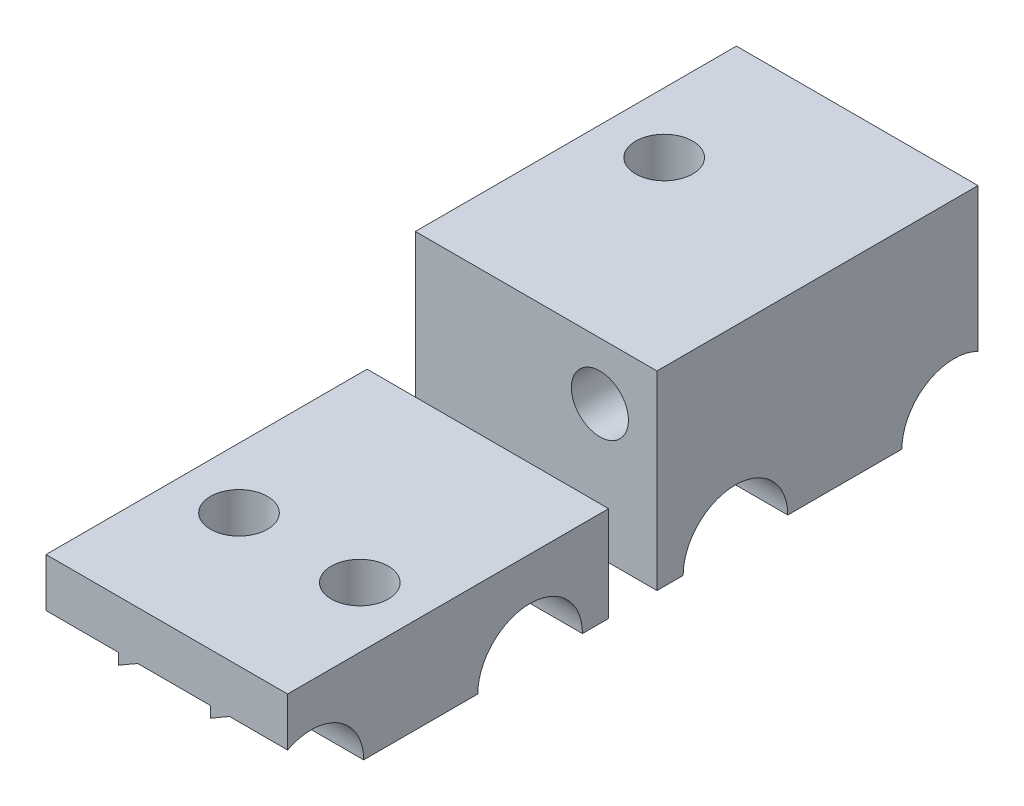
SolidWorks part; units mm, degrees
ref_plane "Front Plane" through (0, 0, 0) normal (0, 0, 1) x (1, 0, 0)
ref_plane "Top Plane" through (0, 0, 0) normal (0, 1, 0) x (1, 0, 0)
ref_plane "Right Plane" through (0, 0, 0) normal (1, 0, 0) x (0, 0, -1)
sketch "Sketch6" plane through (0, 0, 0) normal (0, 1, 0) x (1, 0, 0)
  line L0 (0, 0) -> (0, 5)
  line L1 (0, 5) -> (12.7, 5)
  line L2 (12.7, 5) -> (12.7, 2.75)
  line L6 (12.7, 2.75) -> (9.652, 2.75)
  line L7 (9.652, 2.75) -> (8.636, 2.242)
  line L8 (8.636, 2.242) -> (8.636, 2.75)
  line L9 (8.636, 2.75) -> (4.826, 2.75)
  line L10 (4.826, 2.75) -> (3.81, 2.242)
  line L11 (3.81, 2.242) -> (3.81, 2.75)
  line L12 (3.81, 2.75) -> (0, 2.75)
  line L18 (0, 0) -> (15, 0)
  dimension "D1" = 0.508
  dimension "D2" = 12.7
  dimension "D3" = 3.048
  dimension "D4" = 5
  dimension "D5" = 2.25
  dimension "D6" = 2.25
  dimension "D7" = 2.25
  dimension "D10" = 1.016
  dimension "D11" = 1.016
  dimension "D12" = 3.81
  dimension "D13" = 3.81
  dimension "D20" = 15
revolve "Revolve1" add sketch "Sketch6" angle 180 about L18 region at (6.3538, 0, -3.852)
sketch "Sketch9" plane through (0, 0, 0) normal (0, 0, 1) x (1, 0, 0)
  line L0 (0, 0) -> (0, 3.25)
  line L1 (0, 3.25) -> (0, 5)
  line L2 (0, 5) -> (12.7, 5)
  line L3 (12.7, 5) -> (12.7, 2.75)
  line L4 (12.7, 2.75) -> (12.7, 0)
  line L5 (12.7, 0) -> (0, 0)
  line L6 (0, 3.25) -> (12.7, 2.75)
  dimension "D1" = 3.25
extrude "Boss-Extrude1" add sketch "Sketch9" along normal blind 9.25 and the other way blind 9.25 contours L1 L6 L3 L2 region at (6.6146, 3.9948, 0)
extrude "Boss-Extrude2" add sketch "Sketch9<3>" along normal blind 5.75 from offset 3.5 contours L6 L0 L5 L4 region at (6.1736, 1.5035, 0)
sketch "Sketch9<3>" plane through (0, 0, 0) normal (0, 0, 1) x (1, 0, 0) same geometry as "Sketch9"
extrude "Boss-Extrude3" add sketch "Sketch9<4>" against normal blind 5.75 from offset 3.5 contours L6 L0 L5 L4 region at (6.1736, 1.5035, 0) offset against normal yes
sketch "Sketch9<4>" plane through (0, 0, 0) normal (0, 0, 1) x (1, 0, 0) same geometry as "Sketch9"
sketch "Sketch14" plane through (0, 0, 0) normal (-1, 0, 0) x (0, 0, 1)
  line L0 (-9.25, 5) -> (9.25, 5) construction
  line L1 (-9.25, 0) -> (-6.75, 0)
  line L2 (-9.25, 0) -> (-9.25, 5)
  line L3 (-9.25, 5) -> (-6.75, 5)
  line L4 (-6.75, 0) -> (-6.75, 5)
  dimension "D1" = 2.5
extrude "Cut-Extrude10" cut sketch "Sketch14" against normal through all
ref_plane "Plane3" through (0, 0, -5.75) normal (0, 0, 1) x (1, 0, 0)
mirror "Mirror4" about plane through (0, 0, -5.75) normal (0, 0, 1) of bodies 150 146
sketch "Sketch13" plane through (0, 0, 0) normal (-1, 0, 0) x (0, 0, 1)
  line L0 (-2.75, 0) -> (-8.75, 0) construction
  line L1 (-2.75, 0) -> (2.75, 0)
  line L2 (-2.75, 0) -> (-2.75, 2.75)
  line L3 (-2.75, 2.75) -> (2.75, 2.75)
  line L4 (2.75, 0) -> (2.75, 2.75)
  point P6 (0, 0)
  dimension "D1" = 5.5
  dimension "D2" = 2.75
extrude "Cut-Extrude9" cut sketch "Sketch13" against normal blind 1.75
sketch "Sketch15" plane through (0, 5, 0) normal (0, 1, 0) x (1, 0, 0)
  line L0 (0, 20.75) -> (0, -9.25) construction
  line L1 (12.7, 20.75) -> (0, 20.75)
  line L2 (12.7, 20.75) -> (12.7, 12.75)
  line L3 (12.7, 12.75) -> (0, 12.75)
  line L4 (0, 20.75) -> (0, 12.75)
  dimension "D1" = 8
extrude "Cut-Extrude11" cut sketch "Sketch15" against normal through all
sketch "Sketch16" plane through (0, 0, 0) normal (-1, 0, 0) x (0, 0, 1)
  line L0 (-12.75, 5) -> (9.25, 5) construction
  line L1 (9.25, 0) -> (4.1274, 0)
  line L2 (9.25, 0) -> (9.25, 5)
  line L3 (9.25, 5) -> (4.1274, 5)
  line L4 (4.1274, 0) -> (4.1274, 5)
extrude "Cut-Extrude12" cut sketch "Sketch16" against normal through all
ref_plane "Plane5" through (0, 0, 5.3974) normal (0, 0, 1) x (1, 0, 0)
mirror "Mirror8" about plane through (0, 0, 5.3974) normal (0, 0, 1) of bodies 152
sketch "Sketch17" plane through (0, 5, 0) normal (0, 1, 0) x (1, 0, 0)
  line L1 (0, -4.1274) -> (12.7, -4.1274)
  line L2 (0, -4.1274) -> (0, 12.75)
  line L3 (0, 12.75) -> (12.7, 12.75)
  line L4 (12.7, -4.1274) -> (12.7, 12.75)
extrude "Boss-Extrude4" add sketch "Sketch17" along normal blind 5
sketch "Sketch18" plane through (0, 10, 0) normal (0, 1, 0) x (1, 0, 0)
  line L0 (12.7, -4.1274) -> (12.7, 12.75) construction
  line L1 (0, 12.75) -> (0, -4.1274) construction
  line L2 (0, -4.1274) -> (12.7, -4.1274) construction
  circle A0 centre (3.175, 5.7786) radius 1.5
  circle A1 centre (9.525, 5.7786) radius 1.5
  dimension "D1" = 3
  dimension "D2" = 3
  dimension "D3" = 3.175
  dimension "D4" = 3.175
  dimension "D5" = 9.906
extrude "Cut-Extrude13" cut sketch "Sketch18" against normal through all contours A0 region at (3.175, 10, -5.7786)
sketch "Sketch19" plane through (0, 5, 0) normal (0, 1, 0) x (1, 0, 0)
  line L0 (0, -23.5447) -> (0, -6.6674) construction
  line L1 (12.7, -23.5447) -> (12.7, -6.6674) construction
  line L2 (12.7, -6.6674) -> (0, -6.6674) construction
  circle A0 centre (3.175, -16.5734) radius 1.5
  circle A1 centre (9.525, -16.5734) radius 1.5
  point P8 (0, 0)
  dimension "D3" = 3
  dimension "D4" = 3
  dimension "D1" = 3.175
  dimension "D2" = 3.175
  dimension "D5" = 9.906
extrude "Cut-Extrude14" cut sketch "Sketch19" against normal through all
extrude "Cut-Extrude15" cut sketch "Sketch18<4>" along normal blind 4.445 from surface starting at face at (3.175, 0, -4.2786)
sketch "Sketch18<4>" plane through (0, 10, 0) normal (0, 1, 0) x (1, 0, 0) same geometry as "Sketch18"
sketch "Sketch20" plane through (0, 0, 4.1274) normal (0, 0, 1) x (1, 0, 0)
  line L0 (12.7, 10) -> (12.7, 0) construction
  line L1 (0, 10) -> (12.7, 10) construction
  circle A0 centre (9.7, 7) radius 1.5
  dimension "D1" = 3
  dimension "D2" = 3
  dimension "D3" = 3
extrude "Cut-Extrude16" cut sketch "Sketch20" against normal through all
